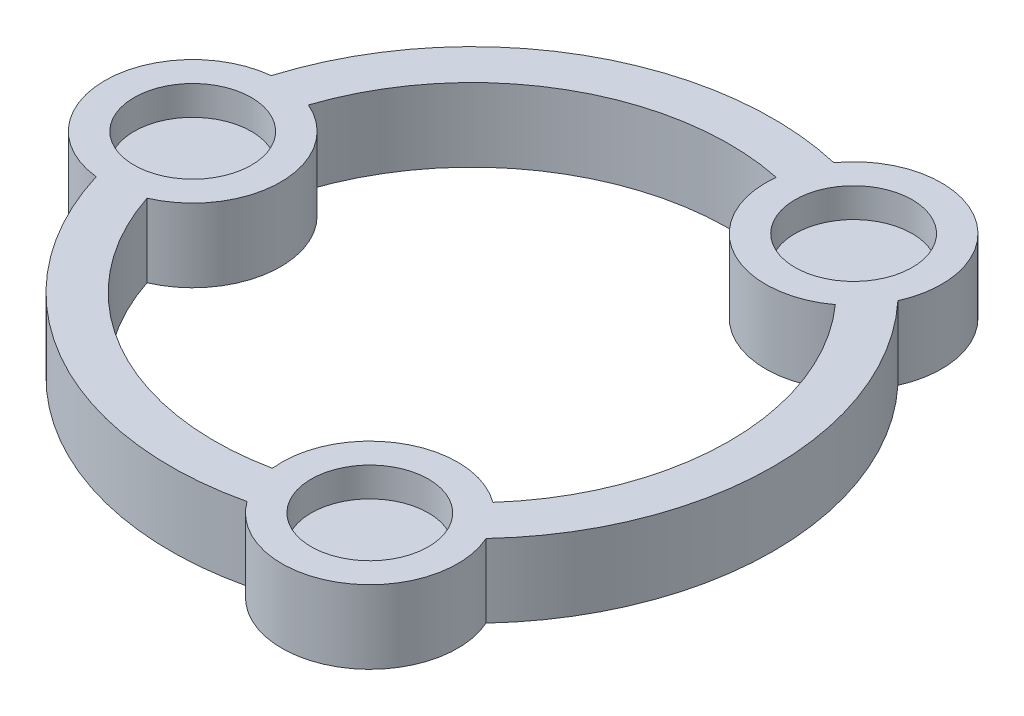
SolidWorks part; units mm, degrees
ref_plane "Front Plane" through (0, 0, 0) normal (0, 0, 1) x (1, 0, 0)
ref_plane "Top Plane" through (0, 0, 0) normal (0, 1, 0) x (1, 0, 0)
ref_plane "Right Plane" through (0, 0, 0) normal (1, 0, 0) x (0, 0, -1)
sketch "Sketch2" plane through (0, 0, 0) normal (0, 1, 0) x (1, 0, 0)
  circle A0 centre (0, 0) radius 26
  point P11 (0, 0)
  dimension "D1" = 52
extrude "Boss-Extrude2" add sketch "Sketch2" along normal blind 5
sketch "Sketch3" plane through (0, 5, 0) normal (0, -1, 0) x (1, 0, 0)
  circle A3 centre (9.5263, -16.4999) radius 4
  circle A4 centre (9.5263, 16.4999) radius 4
  circle A5 centre (-19.0525, 0) radius 4
  circle A6 centre (9.5263, -16.4999) radius 3.175 construction
  circle A7 centre (-19.0525, 0) radius 3.175 construction
  circle A8 centre (9.5263, 16.4999) radius 3.175 construction
  dimension "D1" = 8
  dimension "D2" = 8
  dimension "D3" = 8
extrude "Cut-Extrude1" cut sketch "Sketch3" along normal blind 2
sketch "Sketch5" plane through (0, 5, 0) normal (0, 1, 0) x (1, 0, 0)
  arc A1 (4.663, 20.014) -> (-19.6641, 5.9687) centre (0, 0) ccw
  arc A2 (3.5654, 17.184) -> (-16.6645, 5.5043) centre (0, 0) ccw
  arc A6 (13.0991, -11.6797) -> (3.5654, -17.184) centre (9.5263, -16.4999) ccw
  circle A9 centre (0, 0) radius 26
  arc A11 (-16.6645, -5.5043) -> (3.5654, -17.184) centre (0, 0) ccw
  arc A13 (-19.6641, -5.9687) -> (4.663, -20.014) centre (0, 0) ccw
  arc A14 (15.0011, -14.0452) -> (15.0011, 14.0452) centre (0, 0) ccw
  arc A15 (13.0991, -11.6797) -> (13.0991, 11.6797) centre (0, 0) ccw
  arc A16 (3.5654, 17.184) -> (13.0991, 11.6797) centre (9.5263, 16.4999) ccw
  circle A19 centre (9.5263, -16.4999) radius 6
  arc A20 (4.663, -20.014) -> (15.0011, -14.0452) centre (9.5263, -16.4999) ccw
  circle A22 centre (9.5263, 16.4999) radius 6
  arc A23 (15.0011, 14.0452) -> (4.663, 20.014) centre (9.5263, 16.4999) ccw
  circle A25 centre (-19.0525, 0) radius 6
  arc A26 (-16.6645, -5.5043) -> (-19.6641, -5.9687) centre (-19.0525, 0) ccw
  circle M23 centre (0, 0) radius 26
  dimension "D1" = 2
  dimension "D2" = 2
  dimension "D3" = 2
extrude "Cut-Extrude3" cut sketch "Sketch5" against normal through all contours A15 A2 A11 | A14 A13 A1 M23 region at (0, 5, 0) region at (-25.2646, 5, 0)
